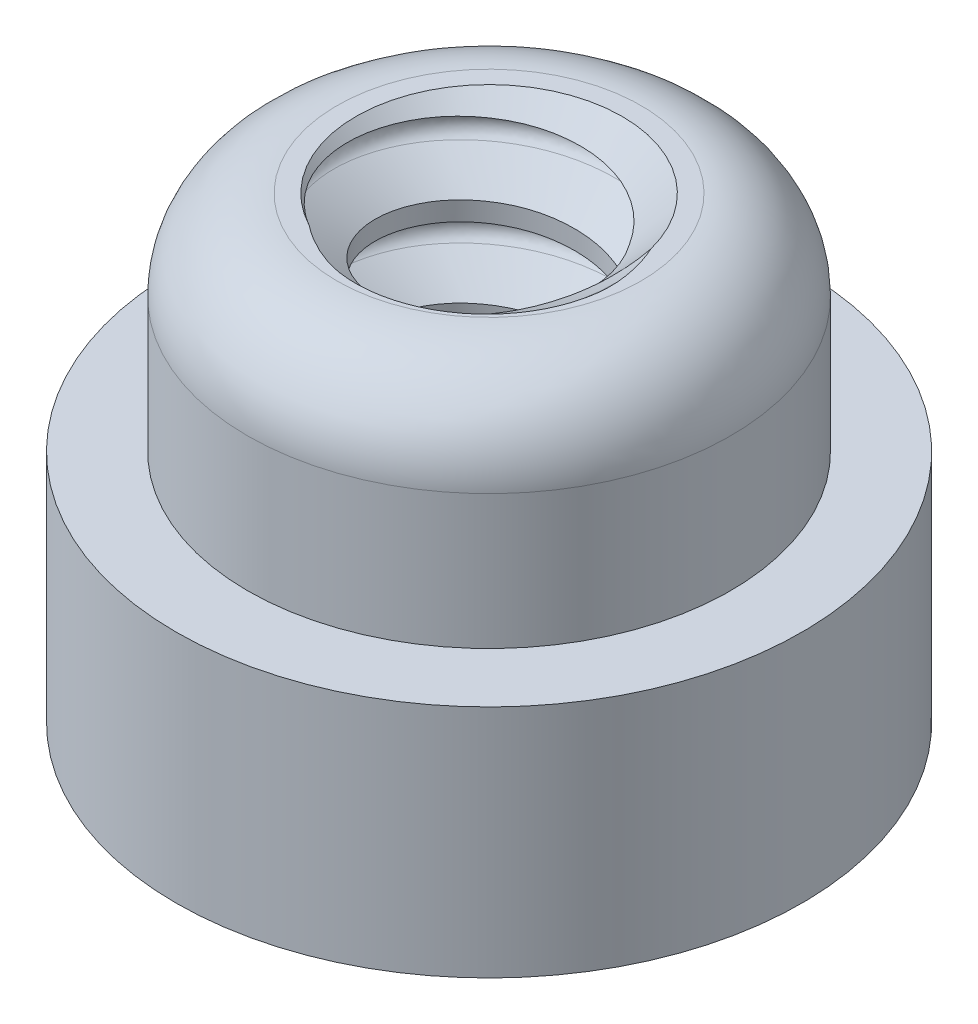
SolidWorks part; units mm, degrees
ref_plane "Ebene vorne" through (0, 0, 0) normal (0, 0, 1) x (1, 0, 0)
ref_plane "Ebene oben" through (0, 0, 0) normal (0, 1, 0) x (1, 0, 0)
ref_plane "Ebene rechts" through (0, 0, 0) normal (1, 0, 0) x (0, 0, -1)
sketch "Skizze1" plane through (0, 0, 0) normal (0, 0, 1) x (1, 0, 0)
  line L0 (0, 12.4554) -> (0, -10.8804) construction
  line L1 (7, 0) -> (2.25, 0)
  line L2 (7, 0) -> (7, 5.25)
  line L3 (7, 5.25) -> (5.4, 5.25)
  line L4 (5.4, 5.25) -> (5.4, 8.25)
  line L5 (3.4, 10.25) -> (2.25, 10.25)
  line L7 (2.25, 10.25) -> (2.25, 0)
  arc A0 (3.4, 10.25) -> (5.4, 8.25) centre (3.4, 8.25) cw
  dimension "D3" = 2
  dimension "D1" = 5.25
  dimension "D2" = 10.25
  dimension "D4" = 10.8
  dimension "D5" = 4.5
  dimension "D6" = 14
revolve "Rotation1" add sketch "Skizze1" angle 360 about L0
sketch "Skizze2" plane through (0, 10.25, 0) normal (0, 1, 0) x (1, 0, 0)
  circle A0 centre (0, 0) radius 2.5
curve "Spirale/Helix1" pitch 2 height 16 radius 2.5 centre (0, 10.25, 0) axis (0, -1, 0) start towards (0, 0, 1)
sketch "Skizze3" plane through (0, 0, 0) normal (1, 0, 0) x (0, 0, -1)
  line L0 (0, 0) -> (0, 16.5592) construction
  line L1 (2.25, 11.8251) -> (3.1641, 11.2974)
  line L2 (3.1641, 10.7778) -> (2.25, 10.25)
  line L3 (2.25, 10.25) -> (2.25, 11.8251)
  line L4 (2.25, 10.25) -> (-2.25, 10.25) construction
  arc A0 (3.1641, 11.2974) -> (3.1641, 10.7778) centre (3.0141, 11.0376) cw
  dimension "D2" = 0.3
  dimension "D1" = 60
  dimension "D3" = 4.5
sweep "Schnitt-Austragung2" cut profiles "Skizze3" path "Spirale/Helix1"
sketch "Skizze4" plane through (0, 0, 0) normal (1, 0, 0) x (0, 0, -1)
  line L0 (-3.29, 10.5618) -> (-1.7657, 9.0376)
  line L1 (-1.7657, 9.0376) -> (-0.2848, 9.0376)
  line L2 (-0.2848, 9.0376) -> (-0.2848, 10.966)
  line L3 (-0.2848, 10.966) -> (-3.29, 10.5618)
  line L4 (0, 0) -> (0, 11.2369) construction
  spline S0 degree 2 poles (0.5223, 10.25) (0.6098, 10.2374) (0.6953, 10.2251) (1.3906, 10.1251) (1.8203, 10.0251) (2.25, 9.9251) (2.25, 9.8251) (2.25, 9.7251) (1.8203, 9.6251) (1.3906, 9.5251) (0.6953, 9.4251) (0, 9.3251) (-0.6953, 9.2251) (-1.3906, 9.1251) (-1.8203, 9.0251) (-2.25, 8.9251) (-2.25, 8.8251) (-2.25, 8.7251) (-1.8203, 8.6251) (-1.3906, 8.5251) (-0.6953, 8.4251) (0, 8.3251) (0.6953, 8.2251) (1.3906, 8.1251) (1.8203, 8.0251) (2.25, 7.9251) (2.25, 7.8251) (2.25, 7.7251) (1.8203, 7.6251) (1.3906, 7.5251) (0.6953, 7.4251) (0, 7.3251) (-0.6953, 7.2251) (-1.3906, 7.1251) (-1.8203, 7.0251) (-2.25, 6.9251) (-2.25, 6.8251) (-2.25, 6.7251) (-1.8203, 6.6251) (-1.3906, 6.5251) (-0.6953, 6.4251) (0, 6.3251) (0.6953, 6.2251) (1.3906, 6.1251) (1.8203, 6.0251) (2.25, 5.9251) (2.25, 5.8251) (2.25, 5.7251) (1.8203, 5.6251) (1.3906, 5.5251) (0.6953, 5.4251) (0, 5.3251) (-0.6953, 5.2251) (-1.3906, 5.1251) (-1.8203, 5.0251) (-2.25, 4.9251) (-2.25, 4.8251) (-2.25, 4.7251) (-1.8203, 4.6251) (-1.3906, 4.5251) (-0.6953, 4.4251) (0, 4.3251) (0.6953, 4.2251) (1.3906, 4.1251) (1.8203, 4.0251) (2.25, 3.9251) (2.25, 3.8251) (2.25, 3.7251) (1.8203, 3.6251) (1.3906, 3.5251) (0.6953, 3.4251) (0, 3.3251) (-0.6953, 3.2251) (-1.3906, 3.1251) (-1.8203, 3.0251) (-2.25, 2.9251) (-2.25, 2.8251) (-2.25, 2.7251) (-1.8203, 2.6251) (-1.3906, 2.5251) (-0.6953, 2.4251) (0, 2.3251) (0.6953, 2.2251) (1.3906, 2.1251) (1.8203, 2.0251) (2.25, 1.9251) (2.25, 1.8251) (2.25, 1.7251) (1.8203, 1.6251) (1.3906, 1.5251) (0.6953, 1.4251) (0, 1.3251) (-0.6953, 1.2251) (-1.3906, 1.1251) (-1.8203, 1.0251) (-2.25, 0.9251) (-2.25, 0.8251) (-2.25, 0.7251) (-1.8203, 0.6251) (-1.3906, 0.5251) (-0.6953, 0.4251) (0, 0.3251) (0.6953, 0.2251) (1.3906, 0.1251) (1.8203, 0.0251) (1.8736, 0.0127) (1.9209, 0) knots 0.098393 0.098393 0.098393 0.1 0.1 0.1125 0.1125 0.125 0.125 0.1375 0.1375 0.15 0.15 0.1625 0.1625 0.175 0.175 0.1875 0.1875 0.2 0.2 0.2125 0.2125 0.225 0.225 0.2375 0.2375 0.25 0.25 0.2625 0.2625 0.275 0.275 0.2875 0.2875 0.3 0.3 0.3125 0.3125 0.325 0.325 0.3375 0.3375 0.35 0.35 0.3625 0.3625 0.375 0.375 0.3875 0.3875 0.4 0.4 0.4125 0.4125 0.425 0.425 0.4375 0.4375 0.45 0.45 0.4625 0.4625 0.475 0.475 0.4875 0.4875 0.5 0.5 0.5125 0.5125 0.525 0.525 0.5375 0.5375 0.55 0.55 0.5625 0.5625 0.575 0.575 0.5875 0.5875 0.6 0.6 0.6125 0.6125 0.625 0.625 0.6375 0.6375 0.65 0.65 0.6625 0.6625 0.675 0.675 0.6875 0.6875 0.7 0.7 0.7125 0.7125 0.725 0.725 0.7375 0.7375 0.739122 0.739122 0.739122 weights 0.989036 0.99371 1 0.951057 1 0.951057 1 0.951057 1 0.951057 1 0.951057 1 0.951057 1 0.951057 1 0.951057 1 0.951057 1 0.951057 1 0.951057 1 0.951057 1 0.951057 1 0.951057 1 0.951057 1 0.951057 1 0.951057 1 0.951057 1 0.951057 1 0.951057 1 0.951057 1 0.951057 1 0.951057 1 0.951057 1 0.951057 1 0.951057 1 0.951057 1 0.951057 1 0.951057 1 0.951057 1 0.951057 1 0.951057 1 0.951057 1 0.951057 1 0.951057 1 0.951057 1 0.951057 1 0.951057 1 0.951057 1 0.951057 1 0.951057 1 0.951057 1 0.951057 1 0.951057 1 0.951057 1 0.951057 1 0.951057 1 0.951057 1 0.951057 1 0.951057 1 0.951057 1 0.99365 0.988948 construction
  spline S1 degree 2 poles (2.25, 10.25) (2.25, 10.15) (1.8203, 10.05) (1.3906, 9.95) (0.6953, 9.85) (0, 9.75) (-0.6953, 9.65) (-1.3906, 9.55) (-1.8203, 9.45) (-2.25, 9.35) (-2.25, 9.25) (-2.25, 9.15) (-1.8203, 9.05) (-1.3906, 8.95) (-0.6953, 8.85) (0, 8.75) (0.6953, 8.65) (1.3906, 8.55) (1.8203, 8.45) (2.25, 8.35) (2.25, 8.25) (2.25, 8.15) (1.8203, 8.05) (1.3906, 7.95) (0.6953, 7.85) (0, 7.75) (-0.6953, 7.65) (-1.3906, 7.55) (-1.8203, 7.45) (-2.25, 7.35) (-2.25, 7.25) (-2.25, 7.15) (-1.8203, 7.05) (-1.3906, 6.95) (-0.6953, 6.85) (0, 6.75) (0.6953, 6.65) (1.3906, 6.55) (1.8203, 6.45) (2.25, 6.35) (2.25, 6.25) (2.25, 6.15) (1.8203, 6.05) (1.3906, 5.95) (0.6953, 5.85) (0, 5.75) (-0.6953, 5.65) (-1.3906, 5.55) (-1.8203, 5.45) (-2.25, 5.35) (-2.25, 5.25) (-2.25, 5.15) (-1.8203, 5.05) (-1.3906, 4.95) (-0.6953, 4.85) (0, 4.75) (0.6953, 4.65) (1.3906, 4.55) (1.8203, 4.45) (2.25, 4.35) (2.25, 4.25) (2.25, 4.15) (1.8203, 4.05) (1.3906, 3.95) (0.6953, 3.85) (0, 3.75) (-0.6953, 3.65) (-1.3906, 3.55) (-1.8203, 3.45) (-2.25, 3.35) (-2.25, 3.25) (-2.25, 3.15) (-1.8203, 3.05) (-1.3906, 2.95) (-0.6953, 2.85) (0, 2.75) (0.6953, 2.65) (1.3906, 2.55) (1.8203, 2.45) (2.25, 2.35) (2.25, 2.25) (2.25, 2.15) (1.8203, 2.05) (1.3906, 1.95) (0.6953, 1.85) (0, 1.75) (-0.6953, 1.65) (-1.3906, 1.55) (-1.8203, 1.45) (-2.25, 1.35) (-2.25, 1.25) (-2.25, 1.15) (-1.8203, 1.05) (-1.3906, 0.95) (-0.6953, 0.85) (0, 0.75) (0.6953, 0.65) (1.3906, 0.55) (1.8203, 0.45) (2.25, 0.35) (2.25, 0.25) (2.25, 0.15) (1.8203, 0.05) (1.7149, 0.0255) (1.5879, 0) knots 0 0 0 0.0125 0.0125 0.025 0.025 0.0375 0.0375 0.05 0.05 0.0625 0.0625 0.075 0.075 0.0875 0.0875 0.1 0.1 0.1125 0.1125 0.125 0.125 0.1375 0.1375 0.15 0.15 0.1625 0.1625 0.175 0.175 0.1875 0.1875 0.2 0.2 0.2125 0.2125 0.225 0.225 0.2375 0.2375 0.25 0.25 0.2625 0.2625 0.275 0.275 0.2875 0.2875 0.3 0.3 0.3125 0.3125 0.325 0.325 0.3375 0.3375 0.35 0.35 0.3625 0.3625 0.375 0.375 0.3875 0.3875 0.4 0.4 0.4125 0.4125 0.425 0.425 0.4375 0.4375 0.45 0.45 0.4625 0.4625 0.475 0.475 0.4875 0.4875 0.5 0.5 0.5125 0.5125 0.525 0.525 0.5375 0.5375 0.55 0.55 0.5625 0.5625 0.575 0.575 0.5875 0.5875 0.6 0.6 0.6125 0.6125 0.625 0.625 0.6375 0.6375 0.640683 0.640683 0.640683 weights 1 0.951057 1 0.951057 1 0.951057 1 0.951057 1 0.951057 1 0.951057 1 0.951057 1 0.951057 1 0.951057 1 0.951057 1 0.951057 1 0.951057 1 0.951057 1 0.951057 1 0.951057 1 0.951057 1 0.951057 1 0.951057 1 0.951057 1 0.951057 1 0.951057 1 0.951057 1 0.951057 1 0.951057 1 0.951057 1 0.951057 1 0.951057 1 0.951057 1 0.951057 1 0.951057 1 0.951057 1 0.951057 1 0.951057 1 0.951057 1 0.951057 1 0.951057 1 0.951057 1 0.951057 1 0.951057 1 0.951057 1 0.951057 1 0.951057 1 0.951057 1 0.951057 1 0.951057 1 0.951057 1 0.951057 1 0.951057 1 0.951057 1 0.951057 1 0.951057 1 0.987537 0.981421 construction
  dimension "D1" = 45
revolve "Schnitt-Rotation1" cut sketch "Skizze4" angle 360 about L4
